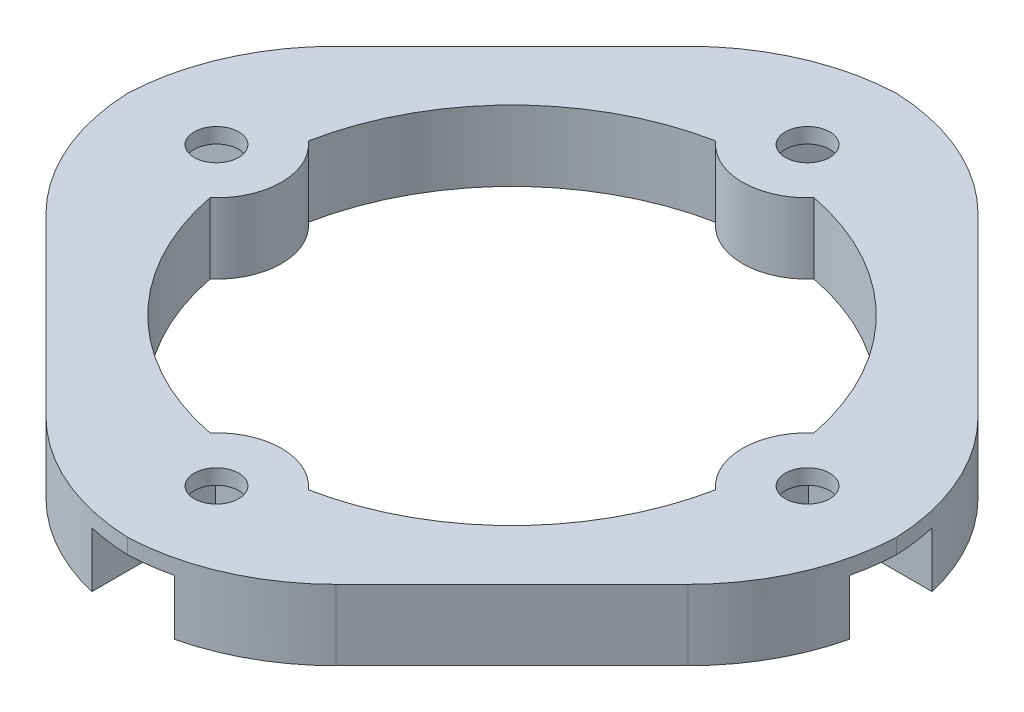
SolidWorks part; units mm, degrees
ref_plane "Спереди" through (0, 0, 0) normal (0, 0, 1) x (1, 0, 0)
ref_plane "Сверху" through (0, 0, 0) normal (0, 1, 0) x (1, 0, 0)
ref_plane "Справа" through (0, 0, 0) normal (1, 0, 0) x (0, 0, -1)
sketch "Sketch1" plane through (0, 0, 0) normal (0, 1, 0) x (1, 0, 0)
  circle A0 centre (0, 0) radius 72.5
  circle A1 centre (0, 0) radius 47.5
  dimension "D1" = 145
  dimension "D2" = 95
extrude "Boss-Extrude1" add sketch "Sketch1" along normal blind 13
sketch "Sketch2" plane through (0, 13, 0) normal (0, 1, 0) x (1, 0, 0)
  line L0 (0, 72.5) -> (0, -72.5) construction
  line L1 (-72.5, 0) -> (72.5, 0) construction
  circle A0 centre (0, 0) radius 72.5 construction
  circle A1 centre (0, 54.5) radius 4.1
  circle A2 centre (54.5, 0) radius 4.1
  circle A3 centre (0, -54.5) radius 4.1
  circle A4 centre (-54.5, 0) radius 4.1
  circle A5 centre (0, 0) radius 54.5 construction
  dimension "D1" = 8.2
  dimension "D2" = 109
extrude "Cut-Extrude1" cut sketch "Sketch2" against normal through all
sketch "Sketch8" plane through (0, 13, 0) normal (0, 1, 0) x (1, 0, 0)
  circle A0 centre (54.5, 0) radius 12
  circle A1 centre (0, -54.5) radius 12
  circle A2 centre (-54.5, 0) radius 12
  circle A3 centre (0, 54.5) radius 12
  circle A4 centre (0, 54.5) radius 4.1
  circle A5 centre (54.5, 0) radius 4.1
  circle A6 centre (0, -54.5) radius 4.1
  circle A7 centre (-54.5, 0) radius 4.1
  circle A8 centre (-54.5, 0) radius 4.1 construction
  point P18 (0, 0)
  dimension "D1" = 24
extrude "Boss-Extrude4" add sketch "Sketch8" against normal up to surface (13 mm away) up to face at (54.5, 0, 4.1)
sketch "Sketch3" plane through (0, 0, 0) normal (0, -1, 0) x (1, 0, 0)
  line L0 (-35.7148, 0) -> (-72.5, 0) construction
  line L1 (7.6, 47.1) -> (-7.6, 47.1)
  line L2 (7.6, 47.1) -> (7.6, 87.1)
  line L3 (7.6, 87.1) -> (-7.6, 87.1)
  line L4 (-7.6, 47.1) -> (-7.6, 87.1)
  line L5 (7.6, 47.1) -> (-7.6, 87.1) construction
  line L6 (7.6, 87.1) -> (-7.6, 47.1) construction
  line L7 (87.1, -7.6) -> (47.1, -7.6)
  line L8 (87.1, -7.6) -> (87.1, 7.6)
  line L9 (87.1, 7.6) -> (47.1, 7.6)
  line L10 (47.1, -7.6) -> (47.1, 7.6)
  line L11 (87.1, -7.6) -> (47.1, 7.6) construction
  line L12 (87.1, 7.6) -> (47.1, -7.6) construction
  line L13 (7.6, -87.1) -> (-7.6, -87.1)
  line L14 (7.6, -87.1) -> (7.6, -47.1)
  line L15 (7.6, -47.1) -> (-7.6, -47.1)
  line L16 (-7.6, -87.1) -> (-7.6, -47.1)
  line L17 (7.6, -87.1) -> (-7.6, -47.1) construction
  line L18 (7.6, -47.1) -> (-7.6, -87.1) construction
  line L19 (-47.1, -7.6) -> (-87.1, -7.6)
  line L20 (-47.1, -7.6) -> (-47.1, 7.6)
  line L21 (-47.1, 7.6) -> (-87.1, 7.6)
  line L22 (-87.1, -7.6) -> (-87.1, 7.6)
  line L23 (-47.1, -7.6) -> (-87.1, 7.6) construction
  line L24 (-47.1, 7.6) -> (-87.1, -7.6) construction
  line L25 (0, -42.5) -> (0, -72.5) construction
  line L26 (42.5, 0) -> (72.5, 0) construction
  line L27 (0, 42.5) -> (0, 54.5) construction
  line L28 (0, 54.5) -> (0, 72.5) construction
  circle A0 centre (0, 0) radius 72.5 construction
  arc A1 (9.0575, -46.6284) -> (-9.0575, -46.6284) centre (0, -54.5) ccw construction
  arc A2 (46.6284, 9.0575) -> (46.6284, -9.0575) centre (54.5, 0) ccw construction
  arc A3 (-9.0575, 46.6284) -> (9.0575, 46.6284) centre (0, 54.5) ccw construction
  circle A4 centre (0, 0) radius 67.1 construction
  point P0 (0, 67.1)
  point P6 (67.1, 0)
  point P12 (0, -67.1)
  point P18 (-67.1, 0)
  dimension "D1" = 15.2
  dimension "D2" = 7.4
  dimension "D3" = 40
extrude "Cut-Extrude2" cut sketch "Sketch3" against normal blind 10.2
sketch "Sketch4" plane through (0, 13, 0) normal (0, 1, 0) x (1, 0, 0)
  line L0 (0, 0) -> (-51.2652, -51.2652) construction
  line L1 (0, 0) -> (0, -72.5) construction
  line L2 (-38.8909, -63.6396) -> (-63.6396, -38.8909)
  line L3 (-63.6396, -38.8909) -> (-62.1237, -37.375)
  line L4 (-62.1237, -37.375) -> (-37.375, -62.1237)
  line L5 (-37.375, -62.1237) -> (-38.8909, -63.6396)
  circle A0 centre (0, 0) radius 72.5 construction
  point P10 (-51.2652, -51.2652)
  dimension "D1" = 45
  dimension "D2" = 35
extrude "Boss-Extrude2" add sketch "Sketch4" against normal up to surface (13 mm away) up to face at (0, 0, 0)
fillet "Fillet1" radius 30 2 edges at (-62.1237, 6.5, 37.375) (-37.375, 6.5, 62.1237)
sketch "Sketch7" plane through (0, 13, 0) normal (0, 1, 0) x (1, 0, 0)
  line L0 (70.9313, -15) -> (15, -70.9313)
  line L1 (15, -70.9313) -> (-15, -70.9313)
  line L2 (-15, -70.9313) -> (-70.9313, -15)
  line L3 (-70.9313, -15) -> (-70.9313, 15)
  line L4 (-70.9313, 15) -> (-15, 70.9313)
  line L5 (-15, 70.9313) -> (15, 70.9313)
  line L6 (15, 70.9313) -> (70.9313, 15)
  line L7 (70.9313, 15) -> (70.9313, -15)
  line L8 (54.5, 0) -> (0, 0) construction
  line L9 (54.5, 0) -> (70.9313, 0) construction
  arc A0 (-29.7524, -66.1139) -> (-66.1139, -29.7524) centre (0, 0) ccw construction
  arc A1 (-29.7524, -66.1139) -> (-66.1139, -29.7524) centre (0, 0) ccw construction
  dimension "D1" = 30
extrude "Cut-Extrude4" cut sketch "Sketch7" against normal through all flip side to cut
fillet "Fillet3" radius 40 8 edges at (15, 6.5, 70.9313) (-15, 6.5, 70.9313) (-70.9313, 6.5, 15) (-70.9313, 6.5, -15) (-15, 6.5, -70.9313) (15, 6.5, -70.9313) (70.9313, 6.5, 15) (70.9313, 6.5, -15)
